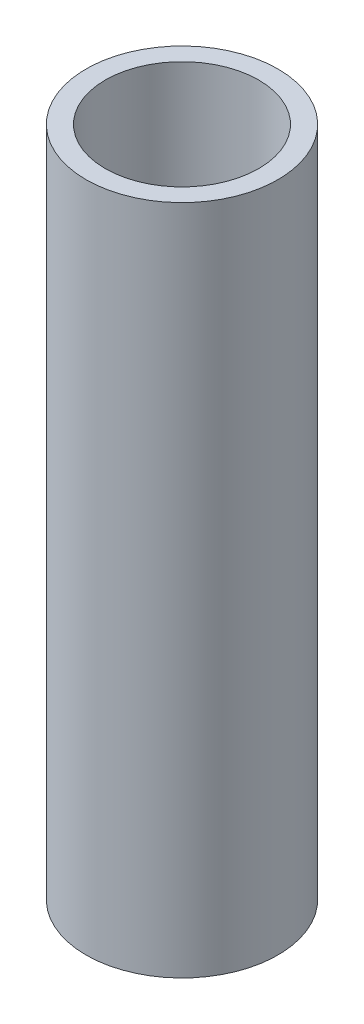
SolidWorks part; units mm, degrees
ref_plane "Alzado" through (0, 0, 0) normal (0, 0, 1) x (1, 0, 0)
ref_plane "Planta" through (0, 0, 0) normal (0, 1, 0) x (1, 0, 0)
ref_plane "Vista lateral" through (0, 0, 0) normal (1, 0, 0) x (0, 0, -1)
sketch "Croquis1" plane through (0, 0, 0) normal (0, 1, 0) x (1, 0, 0)
  circle A0 centre (0, 0) radius 5
  circle A1 centre (0, 0) radius 4
  dimension "D1" = 10
  dimension "D2" = 8
extrude "Saliente-Extruir1" add sketch "Croquis1" along normal blind 35
